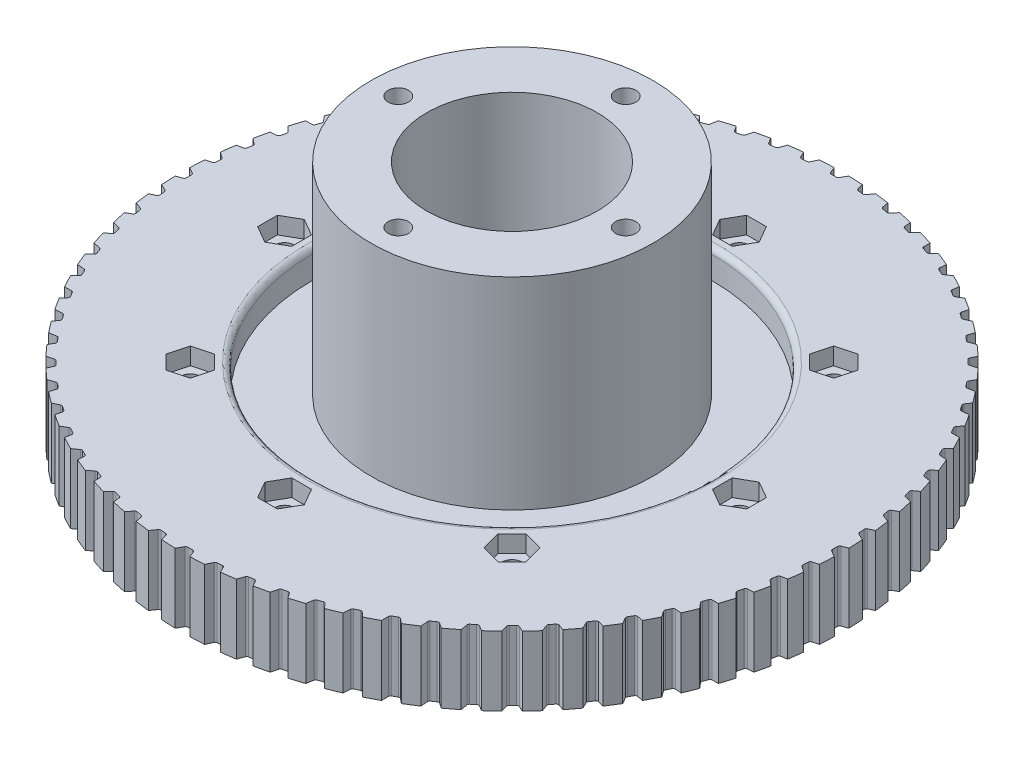
SolidWorks part; units mm, degrees
material "ESUN PLA +"
ref_plane "Front Plane" through (0, 0, 0) normal (0, 0, 1) x (1, 0, 0)
ref_plane "Top Plane" through (0, 0, 0) normal (0, 1, 0) x (1, 0, 0)
ref_plane "Right Plane" through (0, 0, 0) normal (1, 0, 0) x (0, 0, -1)
sketch "Sketch1" plane through (0, 0, 0) normal (0, 1, 0) x (1, 0, 0)
  circle A0 centre (0, 0) radius 57.9628
  dimension "D1" = 115.9256
extrude "Boss-Extrude1" add sketch "Sketch1" along normal blind 12.192
sketch "Sketch2" plane through (0, 12.192, 0) normal (0, 1, 0) x (1, 0, 0)
  line L0 (-1.2827, 57.9628) -> (-1.2827, 83.3628)
  line L1 (1.2827, 57.9628) -> (1.2827, 83.3628)
  line L2 (0, 0) -> (0, 57.9628) construction
  line L3 (-1.2827, 57.9628) -> (1.2827, 57.9628) construction
  line L4 (-0.5537, 56.6928) -> (0.3295, 56.6928)
  line L5 (1.2827, 57.9628) -> (0.6595, 56.8833)
  line L6 (-1.2827, 57.9628) -> (-0.9117, 56.9435)
  line L7 (1.2827, 83.3628) -> (-1.2827, 83.3628)
  arc A0 (0.3295, 56.6928) -> (0.6595, 56.8833) centre (0.3295, 57.0738) ccw
  arc A1 (-0.9117, 56.9435) -> (-0.5537, 56.6928) centre (-0.5537, 57.0738) ccw
  dimension "D3" = 0.381
  dimension "D1" = 50
  dimension "D2" = 20
  dimension "D4" = 2.5654
  dimension "D5" = 25.4
  dimension "D6" = 57.9628
  dimension "D7" = 1.27
extrude "Cut-Extrude1" cut sketch "Sketch2" against normal through all both and the other way through all
pattern_circular "CirPattern1" count 72 over 360 about axis through (0, 12.192, 0) along (0, -1, 0) of "Cut-Extrude1"
sketch "Sketch3" plane through (0, 12.192, 0) normal (0, 1, 0) x (1, 0, 0)
  circle A0 centre (0, 0) radius 24.8
  dimension "D1" = 49.6
extrude "Boss-Extrude2" add sketch "Sketch3" along normal blind 30.5
sketch "Sketch4" plane through (0, 42.692, 0) normal (0, 1, 0) x (1, 0, 0)
  circle A0 centre (0, 0) radius 15
  dimension "D1" = 30
extrude "Cut-Extrude2" cut sketch "Sketch4" against normal through all both and the other way through all
sketch "Sketch5" plane through (0, 0, 0) normal (0, -1, 0) x (1, 0, 0)
  circle A0 centre (0, -40) radius 1.7
  dimension "D1" = 40
  dimension "D2" = 3.4
extrude "Cut-Extrude3" cut sketch "Sketch5" against normal through all both and the other way through all
sketch "Sketch6" plane through (0, 12.192, 0) normal (0, -1, 0) x (1, 0, 0)
  line L0 (0, -40) -> (0, 0) construction
  line L1 (3.4641, -40) -> (1.7321, -37)
  line L2 (1.7321, -37) -> (-1.7321, -37)
  line L3 (-1.7321, -37) -> (-3.4641, -40)
  line L4 (-3.4641, -40) -> (-1.7321, -43)
  line L5 (-1.7321, -43) -> (1.7321, -43)
  line L6 (1.7321, -43) -> (3.4641, -40)
  circle A0 centre (0, -40) radius 3 construction
  point P1 (0, 0)
  dimension "D1" = 6
extrude "Cut-Extrude4" cut sketch "Sketch6" along normal blind 3
pattern_circular "CirPattern2" count 8 over 360 about axis through (0, 0, 0) along (0, 1, 0) of "Cut-Extrude3", "Cut-Extrude4"
sketch "Sketch7" plane through (0, 12.192, 0) normal (0, 1, 0) x (1, 0, 0)
  circle A0 centre (0, 0) radius 24.8
  circle A1 centre (0, 0) radius 35
  circle A2 centre (0, 0) radius 24.8 construction
  dimension "D1" = 70
extrude "Cut-Extrude5" cut sketch "Sketch7" against normal blind 5
fillet "Fillet1" radius 1 1 edges at (0, 12.192, 35)
sketch "Sketch8" plane through (0, 0, 0) normal (0, -1, 0) x (1, 0, 0)
  circle A0 centre (0, -20) radius 1.8
  point P2 (0, 0)
  dimension "D1" = 20
  dimension "D2" = 3.6
extrude "Cut-Extrude6" cut sketch "Sketch8" against normal through all both and the other way through all
pattern_circular "CirPattern3" count 4 over 360 about axis through (0, 0, 0) along (0, 1, 0) of "Cut-Extrude6"
